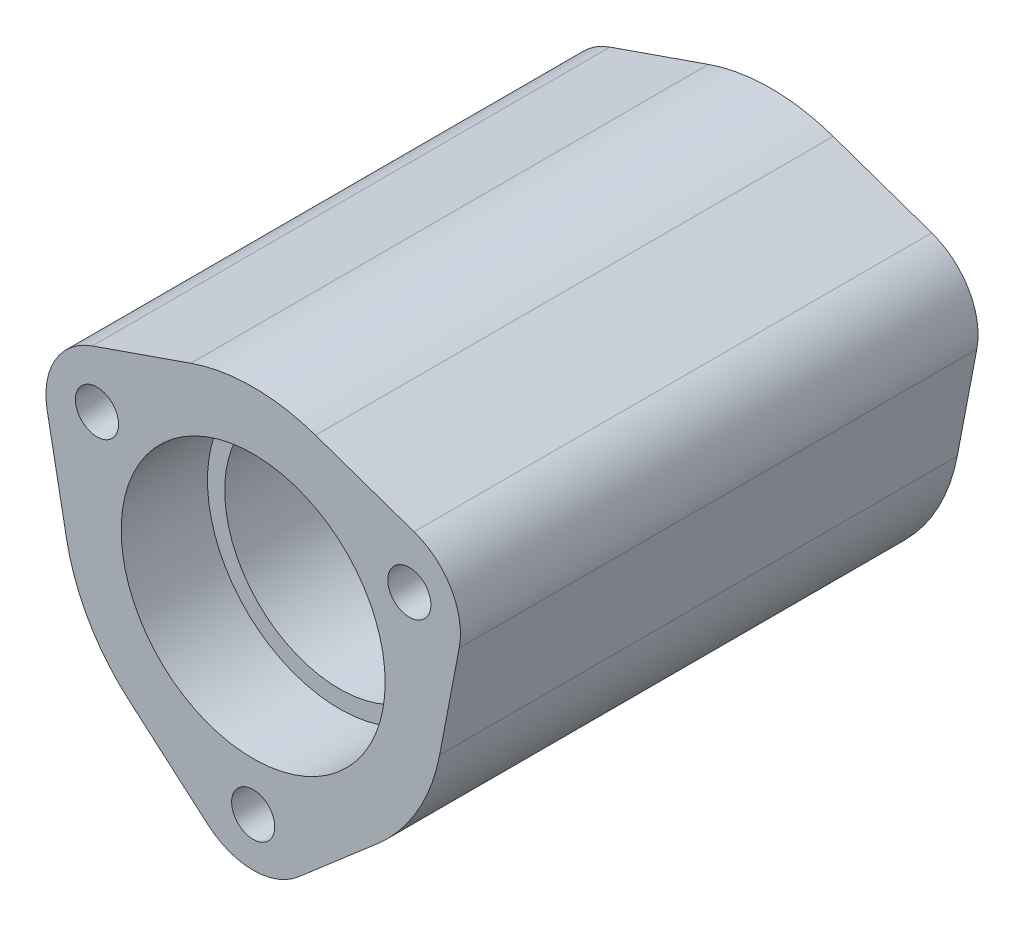
SolidWorks part; units mm, degrees
ref_plane "Спереди" through (0, 0, 0) normal (0, 0, 1) x (1, 0, 0)
ref_plane "Сверху" through (0, 0, 0) normal (0, 1, 0) x (1, 0, 0)
ref_plane "Справа" through (0, 0, 0) normal (1, 0, 0) x (0, 0, -1)
sketch "Эскиз1" plane through (0, 0, 0) normal (0, 0, 1) x (1, 0, 0)
  line L0 (-9.3248, 8.403) -> (-3.6137, 10.3895)
  line L1 (0, 0) -> (0, -9.25) construction
  line L2 (-11.9396, 3.874) -> (-10.8044, -2.0651)
  line L3 (2.6148, -12.277) -> (7.1907, -8.3243)
  line L4 (-2.6148, -12.277) -> (-7.1907, -8.3243)
  line L5 (11.9396, 3.874) -> (10.8044, -2.0651)
  line L6 (9.3248, 8.403) -> (3.6137, 10.3895)
  circle A0 centre (0, 0) radius 11 construction
  arc A1 (7.1907, -8.3243) -> (10.8044, -2.0651) centre (0, 0) ccw
  arc A2 (-9.3248, 8.403) -> (-11.9396, 3.874) centre (-8.0107, 4.625) ccw
  arc A3 (-2.6148, -12.277) -> (2.6148, -12.277) centre (0, -9.25) ccw
  arc A4 (11.9396, 3.874) -> (9.3248, 8.403) centre (8.0107, 4.625) ccw
  arc A5 (3.6137, 10.3895) -> (-3.6137, 10.3895) centre (0, 0) ccw
  arc A6 (-10.8044, -2.0651) -> (-7.1907, -8.3243) centre (0, 0) ccw
  circle A7 centre (0, 0) radius 9.25 construction
  point P24 (0, 0)
  dimension "D1" = 4
  dimension "D2" = 22
  dimension "D3" = 3
  dimension "D4" = 18.5
extrude "тело" add sketch "Эскиз1" along normal blind 15 and the other way blind 15
sketch "Эскиз2" plane through (0, 0, 15) normal (0, 0, 1) x (1, 0, 0)
  circle A0 centre (0, 0) radius 7.65
  dimension "D1" = 15.3
extrude "углубление под подшипник" cut sketch "Эскиз2" against normal blind 5
mirror "Углубление под подшипник с обратной стороны" about plane through (0, 0, 0) normal (0, 0, 1) of "углубление под подшипник"
sketch "Эскиз3" plane through (0, 0, 10) normal (0, 0, 1) x (1, 0, 0)
  circle A0 centre (0, 0) radius 6.65
  circle A1 centre (0, 0) radius 7.65 construction
  dimension "D1" = 1
extrude "сквозное отверстие" cut sketch "Эскиз3" against normal through all
sketch "Эскиз4" plane through (0, 0, 15) normal (0, 0, 1) x (1, 0, 0)
  line L0 (0, -13.25) -> (0, -7.65) construction
  circle A0 centre (-9.05, 5.225) radius 1.25
  circle A1 centre (0, -10.45) radius 1.25
  circle A2 centre (9.05, 5.225) radius 1.25
  arc A3 (-2.6148, -12.277) -> (2.6148, -12.277) centre (0, -9.25) ccw construction
  circle A4 centre (0, 0) radius 7.65 construction
  point P8 (0, 0)
  point P18 (0, -10.45)
  dimension "D1" = 2.5
  dimension "D2" = 3
extrude "отверстия для шурупов" cut sketch "Эскиз4" against normal through all
